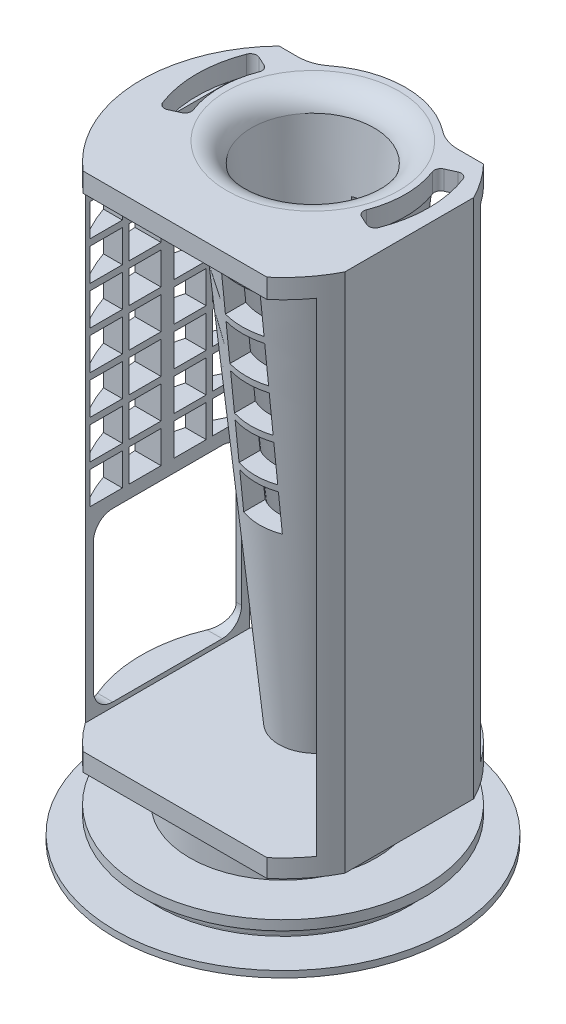
SolidWorks part; units mm, degrees
other "Детальный элемент1"
material "PP Кополимер"
ref_plane "Front Plane" through (0, 0, 0) normal (0, 0, 1) x (1, 0, 0)
ref_plane "Top Plane" through (0, 0, 0) normal (0, 1, 0) x (1, 0, 0)
ref_plane "Right Plane" through (0, 0, 0) normal (1, 0, 0) x (0, 0, -1)
sketch "Эскиз1" plane through (0, 0, 0) normal (0, 1, 0) x (1, 0, 0)
  line L0 (19.6, 9.992) -> (19.6, -9.992)
  line L1 (-14.2632, -16.75) -> (14.2632, -16.75)
  line L2 (-15.8568, 15.25) -> (-12.9239, 15.25)
  line L3 (11.9239, 15.25) -> (15.8568, 15.25)
  line L4 (-0.5, 5.125) -> (-0.5, 23.5612) construction
  line L5 (-0.5, 5.125) -> (-16.8682, 12.625) construction
  line L6 (-14.4479, 11.516) -> (-15.9323, 12.1962)
  line L7 (-14.4479, -1.266) -> (-15.9323, -1.9462)
  line L8 (-0.5, 5.125) -> (-16.8682, -2.375) construction
  line L9 (13.4479, 11.516) -> (14.9323, 12.1962)
  line L10 (13.4479, -1.266) -> (14.9323, -1.9462)
  arc A0 (19.6, 9.992) -> (15.8568, 15.25) centre (0, 0) ccw
  circle A1 centre (-0.5, 5.125) radius 9.5
  arc A2 (8.3046, 16.4881) -> (-9.3046, 16.4881) centre (-0.5, 5.125) ccw
  arc A3 (14.2632, -16.75) -> (19.6, -9.992) centre (0, 0) ccw
  arc A4 (-15.8568, 15.25) -> (-14.2632, -16.75) centre (0, 0) ccw
  arc A5 (-12.9239, 15.25) -> (-9.3046, 16.4881) centre (-12.9239, 21.1592) ccw
  arc A6 (11.9239, 15.25) -> (8.3046, 16.4881) centre (11.9239, 21.1592) cw
  arc A7 (8.3046, 16.4881) -> (-9.3046, 16.4881) centre (-0.5, 5.125) ccw
  arc A9 (-13.9302, 10.2504) -> (-13.9302, -0.0004) centre (-0.5, 5.125) ccw
  arc A10 (-17.2809, 11.6494) -> (-17.2809, -1.3994) centre (-0.5, 5.125) ccw
  arc A11 (-15.9323, -1.9462) -> (-17.2809, -1.3994) centre (-16.3489, -1.0371) cw
  arc A12 (-13.9302, -0.0004) -> (-14.4479, -1.266) centre (-14.8645, -0.3569) cw
  arc A13 (-14.4479, 11.516) -> (-13.9302, 10.2504) centre (-14.8645, 10.6069) cw
  arc A14 (-17.2809, 11.6494) -> (-15.9323, 12.1962) centre (-16.3489, 11.2871) cw
  arc A15 (13.4479, 11.516) -> (12.9302, 10.2504) centre (13.8645, 10.6069) ccw
  arc A16 (16.2809, 11.6494) -> (14.9323, 12.1962) centre (15.3489, 11.2871) ccw
  arc A17 (12.9302, -0.0004) -> (13.4479, -1.266) centre (13.8645, -0.3569) ccw
  arc A18 (14.9323, -1.9462) -> (16.2809, -1.3994) centre (15.3489, -1.0371) ccw
  arc A19 (12.9302, 10.2504) -> (12.9302, -0.0004) centre (-0.5, 5.125) cw
  arc A20 (16.2809, 11.6494) -> (16.2809, -1.3994) centre (-0.5, 5.125) cw
  point P6 (-18.5046, 5.125)
  point P28 (-13.5684, -0.863)
  point P31 (-13.5684, 11.113)
  dimension "D1" = 44
  dimension "D3" = 19
  dimension "D5" = 28.75
  dimension "D9" = 15
  dimension "D10" = 1
  dimension "D2" = 41.6
  dimension "D4" = 10.6
  dimension "D6" = 38.75
  dimension "D7" = 36.25
  dimension "D8" = 32
extrude "основание" add sketch "Эскиз1" along normal blind 3 contours L3 A6 A2 A5 L2 A4 L1 A3 L0 A0 A1 A10 A14 L6 A13 A9 A12 L7 A11 A16 A20 A18 L10 A17 A19 A15 L9 region at (19.0482, 0, 0)
sketch "Эскиз2" plane through (0, 0, 0) normal (0, 1, 0) x (1, 0, 0)
  line L0 (19.6, 9.992) -> (19.6, -9.992) construction
  line L1 (-17.9223, -12.759) -> (17.9223, -12.759) construction
  line L2 (-17.9223, -12.759) -> (-17.9223, 12.759)
  line L3 (-17.9223, 12.759) -> (17.9223, 12.759) construction
  line L4 (17.9223, -12.759) -> (17.9223, 12.759)
  line L5 (-17.9223, -12.759) -> (17.9223, 12.759) construction
  line L6 (-17.9223, 12.759) -> (17.9223, -12.759) construction
  line L7 (19.6, 9.992) -> (19.6, -9.992)
  arc A0 (19.6, 9.992) -> (15.8568, 15.25) centre (0, 0) ccw construction
  arc A1 (-15.8568, 15.25) -> (-14.2632, -16.75) centre (0, 0) ccw construction
  arc A2 (-17.9223, 12.759) -> (-17.9223, -12.759) centre (0, 0) ccw
  arc A3 (14.2632, -16.75) -> (19.6, -9.992) centre (0, 0) ccw construction
  arc A4 (17.9223, -12.759) -> (19.6, -9.992) centre (0, 0) ccw
  arc A5 (19.6, 9.992) -> (17.9223, 12.759) centre (0, 0) ccw
  point P0 (0, 0)
  dimension "D1" = 35.8445
extrude "боковые ребра" add sketch "Эскиз2" against normal blind 75
sketch "Эскиз3" plane through (0, -75, 0) normal (0, -1, 0) x (-1, 0, 0)
  line L0 (14.2632, -16.75) -> (-14.2632, -16.75)
  line L1 (14.2632, -16.75) -> (-14.2632, -16.75) construction
  line L3 (15.8568, 15.25) -> (-7.5223, 20.674)
  line L4 (-19.6, 9.992) -> (-19.6, -9.992)
  line L5 (-19.6, -9.992) -> (-19.6, 9.992) construction
  arc A0 (-7.5223, 20.674) -> (-19.6, 9.992) centre (0, 0) ccw
  arc A1 (-14.2632, -16.75) -> (15.8568, 15.25) centre (0, 0) ccw
  arc A5 (-19.6, -9.992) -> (-14.2632, -16.75) centre (0, 0) ccw
  arc M2 (17.9223, -12.759) -> (17.9223, 12.759) centre (0, 0) ccw
  line M3 (17.9223, 12.759) -> (17.9223, -12.759)
  dimension "D1" = 24
extrude "примыкание ручки" add sketch "Эскиз3" along normal blind 2.8 contours L0 A1 L3 A0 M3 | M3 M2 region at (0.7797, -75, -0.6462) region at (-19.5671, -75, 0)
sketch "Эскиз4" plane through (-17.9223, 0, 0) normal (1, 0, 0) x (0, 0, -1)
  line L0 (0, 0) -> (0, -77.8) construction
  line L1 (9.992, -77.8) -> (-9.992, -77.8) construction
  line L2 (-16.75, -77.8) -> (15.25, -77.8) construction
  line L3 (8.5, -74.3) -> (-8.5, -74.3)
  line L4 (11.5, -71.3) -> (11.5, -51.3)
  line L5 (8.5, -48.3) -> (-8.5, -48.3)
  line L6 (-11.5, -71.3) -> (-11.5, -51.3)
  line L7 (11.5, -74.3) -> (-11.5, -48.3) construction
  line L8 (11.5, -48.3) -> (-11.5, -74.3) construction
  line L9 (12, -41.3) -> (12, -46.3)
  line L10 (6, -41.3) -> (1, -41.3)
  line L11 (6, -41.3) -> (6, -46.3)
  line L12 (6, -46.3) -> (1, -46.3)
  line L13 (1, -41.3) -> (1, -46.3)
  line L14 (6, -41.3) -> (1, -46.3) construction
  line L15 (6, -46.3) -> (1, -41.3) construction
  line L16 (12, -41.3) -> (7, -41.3)
  line L17 (7, -41.3) -> (7, -46.3)
  line L18 (12, -46.3) -> (7, -46.3)
  line L19 (-6, -46.3) -> (-1, -46.3)
  line L20 (-12, -46.3) -> (-7, -46.3)
  line L21 (-6, -46.3) -> (-1, -41.3) construction
  line L22 (-6, -41.3) -> (-1, -46.3) construction
  line L23 (-7, -41.3) -> (-7, -46.3)
  line L24 (-12, -41.3) -> (-7, -41.3)
  line L25 (-1, -41.3) -> (-1, -46.3)
  line L26 (-6, -41.3) -> (-6, -46.3)
  line L27 (-6, -41.3) -> (-1, -41.3)
  line L28 (-12, -41.3) -> (-12, -46.3)
  line L29 (12, -35.3) -> (12, -40.3)
  line L30 (6, -35.3) -> (1, -35.3)
  line L31 (6, -35.3) -> (6, -40.3)
  line L32 (6, -40.3) -> (1, -40.3)
  line L33 (1, -35.3) -> (1, -40.3)
  line L34 (12, -35.3) -> (7, -35.3)
  line L35 (7, -35.3) -> (7, -40.3)
  line L36 (12, -40.3) -> (7, -40.3)
  line L37 (-6, -40.3) -> (-1, -40.3)
  line L38 (-12, -40.3) -> (-7, -40.3)
  line L39 (-7, -35.3) -> (-7, -40.3)
  line L40 (-12, -35.3) -> (-7, -35.3)
  line L41 (-1, -35.3) -> (-1, -40.3)
  line L42 (-6, -35.3) -> (-6, -40.3)
  line L43 (-6, -35.3) -> (-1, -35.3)
  line L44 (-12, -35.3) -> (-12, -40.3)
  line L45 (6, -35.3) -> (1, -40.3) construction
  line L46 (6, -40.3) -> (1, -35.3) construction
  line L47 (-6, -40.3) -> (-1, -35.3) construction
  line L48 (-6, -35.3) -> (-1, -40.3) construction
  line L49 (12, -29.3) -> (12, -34.3)
  line L50 (6, -29.3) -> (1, -29.3)
  line L51 (6, -29.3) -> (6, -34.3)
  line L52 (6, -34.3) -> (1, -34.3)
  line L53 (1, -29.3) -> (1, -34.3)
  line L54 (12, -29.3) -> (7, -29.3)
  line L55 (7, -29.3) -> (7, -34.3)
  line L56 (12, -34.3) -> (7, -34.3)
  line L57 (-6, -34.3) -> (-1, -34.3)
  line L58 (-12, -34.3) -> (-7, -34.3)
  line L59 (-7, -29.3) -> (-7, -34.3)
  line L60 (-12, -29.3) -> (-7, -29.3)
  line L61 (-1, -29.3) -> (-1, -34.3)
  line L62 (-6, -29.3) -> (-6, -34.3)
  line L63 (-6, -29.3) -> (-1, -29.3)
  line L64 (-12, -29.3) -> (-12, -34.3)
  line L65 (6, -29.3) -> (1, -34.3) construction
  line L66 (6, -34.3) -> (1, -29.3) construction
  line L67 (-6, -34.3) -> (-1, -29.3) construction
  line L68 (-6, -29.3) -> (-1, -34.3) construction
  line L69 (12, -23.3) -> (12, -28.3)
  line L70 (6, -23.3) -> (1, -23.3)
  line L71 (6, -23.3) -> (6, -28.3)
  line L72 (6, -28.3) -> (1, -28.3)
  line L73 (1, -23.3) -> (1, -28.3)
  line L74 (12, -23.3) -> (7, -23.3)
  line L75 (7, -23.3) -> (7, -28.3)
  line L76 (12, -28.3) -> (7, -28.3)
  line L77 (-6, -28.3) -> (-1, -28.3)
  line L78 (-12, -28.3) -> (-7, -28.3)
  line L79 (-7, -23.3) -> (-7, -28.3)
  line L80 (-12, -23.3) -> (-7, -23.3)
  line L81 (-1, -23.3) -> (-1, -28.3)
  line L82 (-6, -23.3) -> (-6, -28.3)
  line L83 (-6, -23.3) -> (-1, -23.3)
  line L84 (-12, -23.3) -> (-12, -28.3)
  line L85 (6, -23.3) -> (1, -28.3) construction
  line L86 (6, -28.3) -> (1, -23.3) construction
  line L87 (-6, -28.3) -> (-1, -23.3) construction
  line L88 (-6, -23.3) -> (-1, -28.3) construction
  line L89 (12, -17.3) -> (12, -22.3)
  line L90 (6, -17.3) -> (1, -17.3)
  line L91 (6, -17.3) -> (6, -22.3)
  line L92 (6, -22.3) -> (1, -22.3)
  line L93 (1, -17.3) -> (1, -22.3)
  line L94 (12, -17.3) -> (7, -17.3)
  line L95 (7, -17.3) -> (7, -22.3)
  line L96 (12, -22.3) -> (7, -22.3)
  line L97 (-6, -22.3) -> (-1, -22.3)
  line L98 (-12, -22.3) -> (-7, -22.3)
  line L99 (-7, -17.3) -> (-7, -22.3)
  line L100 (-12, -17.3) -> (-7, -17.3)
  line L101 (-1, -17.3) -> (-1, -22.3)
  line L102 (-6, -17.3) -> (-6, -22.3)
  line L103 (-6, -17.3) -> (-1, -17.3)
  line L104 (-12, -17.3) -> (-12, -22.3)
  line L105 (6, -17.3) -> (1, -22.3) construction
  line L106 (6, -22.3) -> (1, -17.3) construction
  line L107 (-6, -22.3) -> (-1, -17.3) construction
  line L108 (-6, -17.3) -> (-1, -22.3) construction
  line L109 (12, -11.3) -> (12, -16.3)
  line L110 (6, -11.3) -> (1, -11.3)
  line L111 (6, -11.3) -> (6, -16.3)
  line L112 (6, -16.3) -> (1, -16.3)
  line L113 (1, -11.3) -> (1, -16.3)
  line L114 (12, -11.3) -> (7, -11.3)
  line L115 (7, -11.3) -> (7, -16.3)
  line L116 (12, -16.3) -> (7, -16.3)
  line L117 (-6, -16.3) -> (-1, -16.3)
  line L118 (-12, -16.3) -> (-7, -16.3)
  line L119 (-7, -11.3) -> (-7, -16.3)
  line L120 (-12, -11.3) -> (-7, -11.3)
  line L121 (-1, -11.3) -> (-1, -16.3)
  line L122 (-6, -11.3) -> (-6, -16.3)
  line L123 (-6, -11.3) -> (-1, -11.3)
  line L124 (-12, -11.3) -> (-12, -16.3)
  line L125 (6, -11.3) -> (1, -16.3) construction
  line L126 (6, -16.3) -> (1, -11.3) construction
  line L127 (-6, -16.3) -> (-1, -11.3) construction
  line L128 (-6, -11.3) -> (-1, -16.3) construction
  line L129 (12, -5.3) -> (12, -10.3)
  line L130 (6, -5.3) -> (1, -5.3)
  line L131 (6, -5.3) -> (6, -10.3)
  line L132 (6, -10.3) -> (1, -10.3)
  line L133 (1, -5.3) -> (1, -10.3)
  line L134 (12, -5.3) -> (7, -5.3)
  line L135 (7, -5.3) -> (7, -10.3)
  line L136 (12, -10.3) -> (7, -10.3)
  line L137 (-6, -10.3) -> (-1, -10.3)
  line L138 (-12, -10.3) -> (-7, -10.3)
  line L139 (-7, -5.3) -> (-7, -10.3)
  line L140 (-12, -5.3) -> (-7, -5.3)
  line L141 (-1, -5.3) -> (-1, -10.3)
  line L142 (-6, -5.3) -> (-6, -10.3)
  line L143 (-6, -5.3) -> (-1, -5.3)
  line L144 (-12, -5.3) -> (-12, -10.3)
  line L145 (6, -5.3) -> (1, -10.3) construction
  line L146 (6, -10.3) -> (1, -5.3) construction
  line L147 (-6, -10.3) -> (-1, -5.3) construction
  line L148 (-6, -5.3) -> (-1, -10.3) construction
  arc A0 (8.5, -74.3) -> (11.5, -71.3) centre (8.5, -71.3) ccw
  arc A1 (-8.5, -74.3) -> (-11.5, -71.3) centre (-8.5, -71.3) cw
  arc A2 (-8.5, -48.3) -> (-11.5, -51.3) centre (-8.5, -51.3) ccw
  arc A3 (11.5, -51.3) -> (8.5, -48.3) centre (8.5, -51.3) ccw
  point P5 (0, -61.3)
  point P24 (3.5, -43.8)
  point P29 (1, -43.8)
  point P42 (-3.5, -43.8)
  point P44 (3.5, -37.8)
  point P62 (-3.5, -37.8)
  point P63 (3.5, -31.8)
  point P80 (-3.5, -31.8)
  point P81 (3.5, -25.8)
  point P98 (-3.5, -25.8)
  point P99 (3.5, -19.8)
  point P116 (-3.5, -19.8)
  point P117 (3.5, -13.8)
  point P134 (-3.5, -13.8)
  point P135 (3.5, -7.8)
  point P152 (-3.5, -7.8)
  dimension "D4" = 3
  dimension "D1" = 23
  dimension "D2" = 26
  dimension "D3" = 3.5
  dimension "D5" = 5
  dimension "D6" = 2
  dimension "D7" = 2
  dimension "D8" = 2
  dimension "D9" = 7
extrude "перфорация боковых стенок" cut sketch "Эскиз4" against normal through all
sketch "Эскиз6" plane through (0, 0, 0) normal (0, -1, 0) x (-1, 0, 0)
  point P0 (0.5, 5.125)
ref_plane "Плоскость1" through (0, 0, -5.125) normal (0, 0, -1) x (-1, 0, 0)
sketch "Эскиз7" plane through (0, 0, -5.125) normal (0, 0, -1) x (-1, 0, 0)
  line L0 (0, 0) -> (0, -75) construction
  line L1 (15.8568, -75) -> (-7.5223, -75) construction
  line L2 (2.736, -75) -> (10, 0)
  line L3 (-8.3046, 0) -> (9.3046, 0) construction
  line L4 (10, 0) -> (13.014, 0)
  line L6 (13.014, 0) -> (5.75, -75)
  line L7 (5.75, -75) -> (2.736, -75)
  line L9 (-9, 0) -> (10, 0) construction
  dimension "D1" = 11.5
  dimension "D2" = 3
revolve "внутрении конус" add sketch "Эскиз7" angle 360 about L0
sketch "Эскиз8" plane through (0, 0, -5.125) normal (0, 0, -1) x (-1, 0, 0)
  line L0 (0, 0) -> (0, -75) construction
  line L1 (15.8568, -75) -> (-7.5223, -75) construction
  line L2 (-8.3046, 0) -> (9.3046, 0) construction
  line L3 (-3, -10) -> (3, -10)
  line L4 (-3, -10) -> (-3, -16)
  line L5 (-3, -16) -> (3, -16)
  line L6 (3, -10) -> (3, -16)
  line L7 (-3, -10) -> (3, -16) construction
  line L8 (-3, -16) -> (3, -10) construction
  line L9 (-3, -17) -> (-3, -23)
  line L10 (-3, -17) -> (3, -17)
  line L11 (-3, -23) -> (3, -23)
  line L12 (3, -17) -> (3, -23)
  line L13 (-3, -24) -> (-3, -30)
  line L14 (-3, -24) -> (3, -24)
  line L15 (-3, -30) -> (3, -30)
  line L16 (3, -24) -> (3, -30)
  line L17 (-3, -31) -> (-3, -37)
  line L18 (-3, -31) -> (3, -31)
  line L19 (-3, -37) -> (3, -37)
  line L20 (3, -31) -> (3, -37)
  line L21 (-3, -38) -> (-3, -44)
  line L22 (-3, -38) -> (3, -38)
  line L23 (-3, -44) -> (3, -44)
  line L24 (3, -38) -> (3, -44)
  point P5 (0, -13)
  dimension "D1" = 6
  dimension "D2" = 10
  dimension "D3" = 5
extrude "перфорация конуса" cut sketch "Эскиз8" against normal through all both and the other way through all
fillet "Скруг основ конуса" radius 4 1 edges at (-0.5, 3, 4.375)
sketch "Эскиз9" plane through (0, -77.8, 0) normal (0, -1, 0) x (1, 0, 0)
  circle A0 centre (0, 0) radius 14.4801
extrude "шейка ручки" add sketch "Эскиз9" along normal blind 5.5
sketch "Эскиз10" plane through (0, -83.3, 0) normal (0, -1, 0) x (1, 0, 0)
  circle A0 centre (0, 0) radius 22
  dimension "D1" = 44
extrude "бортик перед прокладкой" add sketch "Эскиз10" along normal blind 1.5
sketch "Эскиз11" plane through (0, -84.8, 0) normal (0, -1, 0) x (1, 0, 0)
  circle A0 centre (0, 0) radius 19.5
  dimension "D1" = 39
extrude "прокладка паз" add sketch "Эскиз11" along normal blind 2.5
sketch "Эскиз12" plane through (0, -87.3, 0) normal (0, -1, 0) x (-1, 0, 0)
  circle A0 centre (0, 0) radius 26
  dimension "D1" = 52
extrude "бортик после прокладки" add sketch "Эскиз12" along normal blind 1
sketch "Эскиз13" plane through (0, -88.3, 0) normal (0, -1, 0) x (1, 0, 0)
  circle A0 centre (0, 0) radius 12
extrude "вырез под внеш ручку" cut sketch "Эскиз13" against normal blind 11
chamfer "фаска под ручку " distance 8 distance2 5 1 edges at (0, -88.3, -12) first distance on face at (0, -88.3, -12)
sketch "Эскиз14" plane through (0, -77.3, 0) normal (0, -1, 0) x (1, 0, 0)
  line L0 (0, 0) -> (-8, 9.6047) construction
  line L1 (0, 0) -> (8, 9.6047) construction
  line L2 (-8, 9.6047) -> (-7.36, 8.8363)
  line L3 (8, 9.6047) -> (7.36, 8.8363)
  line L4 (0, 0) -> (0, 16.9399) construction
  line L5 (9.6047, 8) -> (8.8363, 7.36)
  line L6 (9.6047, -8) -> (8.8363, -7.36)
  line L7 (8, -9.6047) -> (7.36, -8.8363)
  line L8 (-8, -9.6047) -> (-7.36, -8.8363)
  line L9 (-9.6047, -8) -> (-8.8363, -7.36)
  line L10 (-9.6047, 8) -> (-8.8363, 7.36)
  arc A0 (7.36, 8.8363) -> (-7.36, 8.8363) centre (0, 0) ccw
  arc A1 (8, 9.6047) -> (-8, 9.6047) centre (0, 0) ccw
  arc A2 (8.8363, -7.36) -> (8.8363, 7.36) centre (0, 0) ccw
  arc A3 (9.6047, -8) -> (9.6047, 8) centre (0, 0) ccw
  arc A4 (-7.36, -8.8363) -> (7.36, -8.8363) centre (0, 0) ccw
  arc A5 (-8, -9.6047) -> (8, -9.6047) centre (0, 0) ccw
  arc A6 (-8.8363, 7.36) -> (-8.8363, -7.36) centre (0, 0) ccw
  arc A7 (-9.6047, 8) -> (-9.6047, -8) centre (0, 0) ccw
  point P22 (0, 0)
  dimension "D1" = 23
  dimension "D2" = 16
  dimension "D3" = 25
  dimension "D4" = 4
extrude "защелки для ручки" add sketch "Эскиз14" along normal blind 3 from offset 5
chamfer "Фаска2" distance 2 distance2 0.8 4 edges at (0, -85.3, -11.5) (11.5, -85.3, 0) (0, -85.3, 11.5) (-11.5, -85.3, 0) first distance on face at (0, -83.8, -10.1682) first distance on face at (10.1682, -83.8, 0) first distance on face at (0, -83.8, 10.1682) first distance on face at (-10.1682, -83.8, 0)
fillet "Скругление1" radius 2 1 edges at (0, -77.8, -14.4801)
fillet "Скругление2" radius 2.3 1 edges at (0, -84.8, -19.5)
